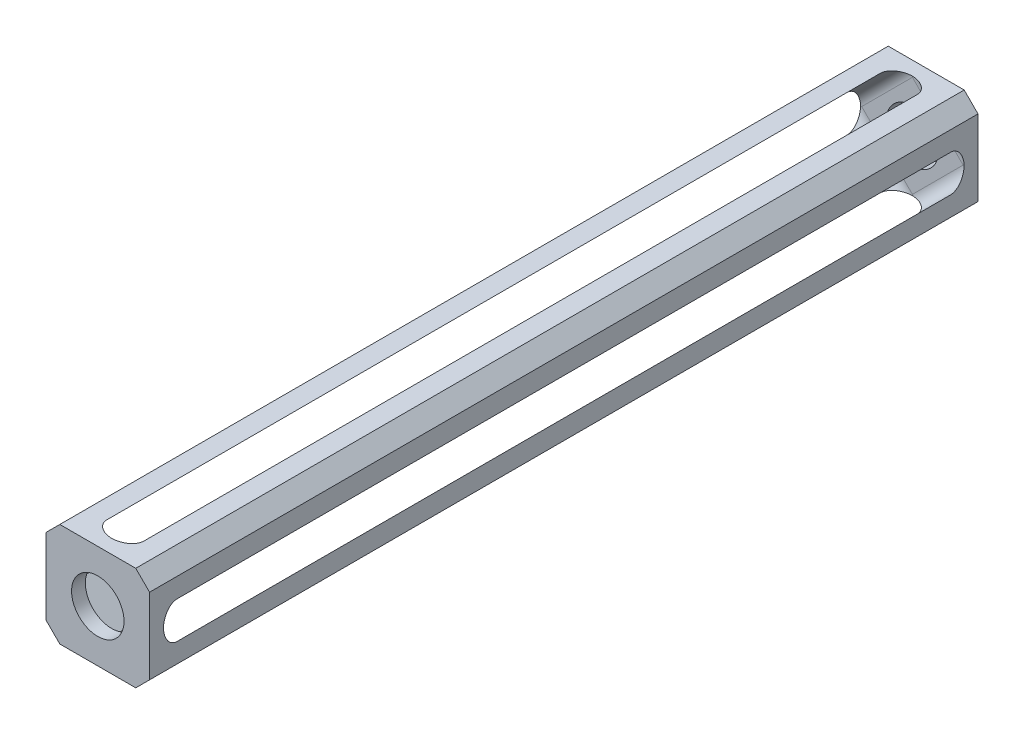
SolidWorks part; units mm, degrees
ref_plane "Front" through (0, 0, 0) normal (0, 0, 1) x (1, 0, 0)
ref_plane "Top" through (0, 0, 0) normal (0, 1, 0) x (1, 0, 0)
ref_plane "Right" through (0, 0, 0) normal (1, 0, 0) x (0, 0, -1)
sketch "Sketch1" plane through (0, 0, 0) normal (0, 0, 1) x (1, 0, 0)
  line L1 (-9.525, 9.525) -> (9.525, 9.525)
  line L2 (-9.525, 9.525) -> (-9.525, -9.525)
  line L3 (-9.525, -9.525) -> (9.525, -9.525)
  line L4 (9.525, 9.525) -> (9.525, -9.525)
  line L5 (-9.525, 9.525) -> (9.525, -9.525) construction
  line L6 (-9.525, -9.525) -> (9.525, 9.525) construction
  point P0 (0, 0)
  dimension "D1" = 19.05
  dimension "D2" = 19.05
extrude "Boss-Extrude1" add sketch "Sketch1" along normal mid plane 152.4
chamfer "Chamfer1" distance 2.54 angle 45 4 edges at (-9.525, -9.525, 0) (9.525, -9.525, 0) (-9.525, 9.525, 0) (9.525, 9.525, 0)
shell "Shell1" thickness 2.54 removed face at (0, -9.525, 0) removed face at (-9.525, 0, 0) removed face at (0, 9.525, 0) removed face at (9.525, 0, 0)
fillet "Fillet1" radius 2.54 8 edges at (-6.4589, 6.4589, -73.66) (6.4589, -6.4589, -73.66) (6.4589, 6.4589, -73.66) (-6.4589, -6.4589, -73.66) (-6.4589, 6.4589, 73.66) (6.4589, 6.4589, 73.66) (6.4589, -6.4589, 73.66) (-6.4589, -6.4589, 73.66)
sketch "Sketch3" plane through (0, 0, 76.2) normal (0, 0, 1) x (1, 0, 0)
  circle A0 centre (0, 0) radius 4.826
  dimension "D1" = 9.652
extrude "Cut-Extrude1" cut sketch "Sketch3" against normal through all
